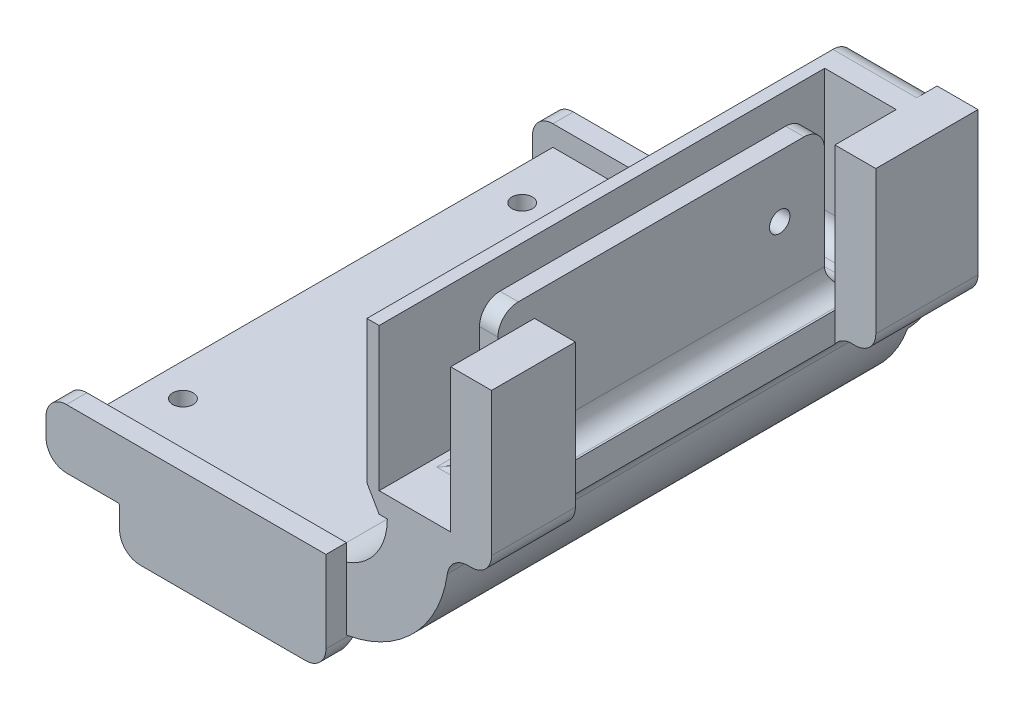
SolidWorks part; units mm, degrees
ref_plane "Alzado" through (0, 0, 0) normal (0, 0, 1) x (1, 0, 0)
ref_plane "Planta" through (0, 0, 0) normal (0, 1, 0) x (1, 0, 0)
ref_plane "Vista lateral" through (0, 0, 0) normal (1, 0, 0) x (0, 0, -1)
sketch "Croquis1" plane through (0, 0, 0) normal (0, 0, 1) x (1, 0, 0)
  line L0 (0, 0) -> (0, -5)
  line L1 (15, -20) -> (337, -20)
  line L2 (352, -5) -> (352, 0)
  line L3 (-15, 0) -> (-15, -5)
  line L4 (15, -35) -> (337, -35)
  line L5 (367, -5) -> (367, 0)
  line L6 (-15, 0) -> (0, 0)
  line L7 (352, 0) -> (367, 0)
  arc A0 (352, -5) -> (337, -20) centre (337, -5) cw
  arc A1 (0, -5) -> (15, -20) centre (15, -5) ccw
  arc A2 (-15, -5) -> (15, -35) centre (15, -5) ccw
  arc A3 (367, -5) -> (337, -35) centre (337, -5) cw
  dimension "D1" = 15
  dimension "D2" = 5
  dimension "D4" = 352
  dimension "D3" = 15
extrude "Saliente-Extruir1" add sketch "Croquis1" along normal blind 103
sketch "Croquis2" plane through (0, 0, 0) normal (0, 1, 0) x (1, 0, 0)
  line L0 (0, -103) -> (0, 0) construction
  line L1 (-10, -25.1459) -> (-5, -25.1459)
  line L2 (-10, -25.1459) -> (-10, -75.1459)
  line L3 (-10, -75.1459) -> (-5, -75.1459)
  line L4 (-5, -25.1459) -> (-5, -75.1459)
  line L5 (357, -11.55) -> (362, -11.55)
  line L6 (357, -11.55) -> (357, -91.45)
  line L7 (357, -91.45) -> (362, -91.45)
  line L8 (362, -11.55) -> (362, -91.45)
  line L9 (352, -103) -> (352, 0) construction
  line L10 (352, 0) -> (352, -103) construction
  point P12 (362, -51.5)
  point P17 (352, -51.5)
  dimension "D1" = 5
  dimension "D2" = 50
  dimension "D3" = 5
  dimension "D4" = 79.9
  dimension "D5" = 5
  dimension "D6" = 5
extrude "Saliente-Extruir2" add sketch "Croquis2" along normal blind 35
fillet "Redondeo1" radius 5 8 edges at (362, 0, 51.5) (359.5, 0, 91.45) (357, 0, 51.5) (359.5, 0, 11.55) (-7.5, 0, 25.1459) (-10, 0, 50.1459) (-7.5, 0, 75.1459) (-5, 0, 50.1459)
fillet "Redondeo2" radius 5 4 edges at (-7.5, 35, 25.1459) (-7.5, 35, 75.1459) (359.5, 35, 11.55) (359.5, 35, 91.45)
ref_plane "Plano1" through (15, 0, 0) normal (1, 0, 0) x (0, 0, -1)
sketch "Croquis3" plane through (15, 0, 0) normal (1, 0, 0) x (0, 0, -1)
  line L0 (-103, -35) -> (0, -35) construction
  line L1 (-76.5, -35) -> (-70.5, -35)
  line L2 (-76.5, -35) -> (-76.5, -43)
  line L3 (-76.5, -43) -> (-26.5, -43)
  line L4 (-26.5, -35) -> (-26.5, -43)
  line L5 (-103, -35) -> (-70.5, -35) construction
  line L6 (-51.5, -33) -> (-51.5, -5) construction
  line L7 (-103, -5) -> (0, -5) construction
  line L8 (-32.5, -35) -> (-26.5, -35)
  line L10 (-70.5, -35) -> (-70.5, -39)
  line L11 (-70.5, -39) -> (-32.5, -39)
  line L12 (-32.5, -35) -> (-32.5, -39)
  line L13 (-51.5, -35) -> (-32.5, -39) construction
  line L14 (-70.5, -39) -> (-51.5, -35) construction
  line L15 (-32.5, -35) -> (0, -35) construction
  dimension "D1" = 50
  dimension "D2" = 8
  dimension "D3" = 38
  dimension "D4" = 4
extrude "Saliente-Extruir3" add sketch "Croquis3" along normal up to vertex (322 mm away) up to point (337, -35, 103)
fillet "Redondeo4" radius 10 2 edges at (176, -35, 76.5) (176, -35, 26.5)
fillet "Redondeo5" radius 10 2 edges at (176, -43, 26.5) (176, -43, 76.5)
sketch "Croquis4" plane through (0, 0, 103) normal (0, 0, 1) x (1, 0, 0)
  line L0 (176, -43) -> (176, 89.8456) construction
  line L1 (337, -43) -> (15, -43) construction
  line L3 (176, 89.8456) -> (296, 89.8456)
  line L4 (176, 89.8456) -> (176, -75.5918)
  line L5 (176, -75.5918) -> (296, -75.5918)
  line L6 (296, 89.8456) -> (296, -75.5918)
  dimension "D1" = 120
extrude "Cortar-Extruir1" cut sketch "Croquis4" against normal through all both and the other way through all
sketch "Croquis8" plane through (296, 0, 0) normal (-1, 0, 0) x (0, 0, 1)
  line L1 (103, -20) -> (0, -20)
  line L2 (103, -20) -> (103, -27)
  line L3 (103, -27) -> (0, -27)
  line L4 (0, -20) -> (0, -27)
  dimension "D1" = 7
extrude "Saliente-Extruir5" add sketch "Croquis8" along normal blind 200
fillet "Redondeo6" radius 15 2 edges at (96, -23.5, 0) (96, -23.5, 103)
sketch "Croquis9" plane through (0, -27, 0) normal (0, -1, 0) x (1, 0, 0)
  line L0 (144.6603, 56.5) -> (147.3397, 56.5)
  line L2 (96, 51.5) -> (106, 51.5) construction
  line L19 (96, 15) -> (96, 88) construction
  line L27 (124.6603, 46.5) -> (127.3397, 46.5)
  line L37 (124.6603, 56.5) -> (127.3397, 56.5)
  line L41 (125.1449, 47.4539) -> (146.3537, 48.864) construction
  line L44 (125.1449, 55.5461) -> (126.807, 55.4356) construction
  line L48 (244.6603, 46.5) -> (247.3397, 46.5)
  line L49 (244.6603, 56.5) -> (247.3397, 56.5)
  line L50 (224.6603, 46.5) -> (227.3397, 46.5)
  line L51 (224.6603, 56.5) -> (227.3397, 56.5)
  line L52 (204.6603, 56.5) -> (207.3397, 56.5)
  line L53 (204.6603, 46.5) -> (207.3397, 46.5)
  line L54 (184.6603, 46.5) -> (187.3397, 46.5)
  line L55 (184.6603, 56.5) -> (187.3397, 56.5)
  line L57 (164.6603, 56.5) -> (167.3397, 56.5)
  line L58 (164.6603, 46.5) -> (167.3397, 46.5)
  line L59 (144.6603, 46.5) -> (147.3397, 46.5)
  arc A21 (124.6603, 56.5) -> (124.6603, 46.5) centre (116, 51.5) ccw
  arc A33 (127.3397, 46.5) -> (144.6603, 46.5) centre (136, 51.5) ccw
  arc A34 (147.3397, 46.5) -> (164.6603, 46.5) centre (156, 51.5) ccw
  arc A35 (167.3397, 46.5) -> (184.6603, 46.5) centre (176, 51.5) ccw
  arc A36 (187.3397, 46.5) -> (204.6603, 46.5) centre (196, 51.5) ccw
  arc A38 (244.6603, 56.5) -> (227.3397, 56.5) centre (236, 51.5) ccw
  arc A39 (247.3397, 46.5) -> (247.3397, 56.5) centre (256, 51.5) ccw
  arc A40 (144.6603, 56.5) -> (127.3397, 56.5) centre (136, 51.5) ccw
  arc A41 (164.6603, 56.5) -> (147.3397, 56.5) centre (156, 51.5) ccw
  arc A42 (184.6603, 56.5) -> (167.3397, 56.5) centre (176, 51.5) ccw
  arc A43 (204.6603, 56.5) -> (187.3397, 56.5) centre (196, 51.5) ccw
  arc A44 (207.3397, 46.5) -> (224.6603, 46.5) centre (216, 51.5) ccw
  arc A45 (227.3397, 46.5) -> (244.6603, 46.5) centre (236, 51.5) ccw
  arc A46 (206.0896, 52.8357) -> (206, 51.5) centre (216, 51.5) ccw [skipped]
  arc A47 (224.6603, 56.5) -> (207.3397, 56.5) centre (216, 51.5) ccw
  point P8 (186, 51.5)
  dimension "D1" = 20
  dimension "D3" = 8
  dimension "D2" = 20
sketch "Croquis10" plane through (362, 0, 0) normal (1, 0, 0) x (0, 0, -1)
  line L0 (-51.5, 35) -> (-51.5, 2.6584) construction
  line L1 (-86.45, 35) -> (-16.55, 35) construction
  line L2 (-80.5, 20) -> (-22.5, 20) construction
  circle A0 centre (-80.5, 20) radius 2.5
  circle A1 centre (-22.5, 20) radius 2.5
  point P4 (-51.5, 20)
  dimension "D1" = 58
  dimension "D3" = 5
  dimension "D4" = 5
  dimension "D2" = 15
extrude "Cortar-Extruir5" cut sketch "Croquis10" against normal through all
extrude "Cortar-Extruir6" cut sketch "Croquis9" against normal blind 10
sketch "Croquis11" plane through (0, -27, 0) normal (0, -1, 0) x (1, 0, 0)
  line L4 (96, 88) -> (96, 15)
  line L5 (111, 0) -> (296, 0)
  line L6 (296, 0) -> (296, 103)
  line L7 (296, 103) -> (111, 103)
  line L8 (96, 88) -> (96, 15)
  line L9 (111, 0) -> (296, 0)
  line L10 (296, 0) -> (296, 103)
  line L11 (296, 103) -> (111, 103)
  arc A2 (96, 15) -> (111, 0) centre (111, 15) ccw
  arc A3 (111, 103) -> (96, 88) centre (111, 88) ccw
  arc A4 (96, 15) -> (111, 0) centre (111, 15) ccw
  arc A5 (111, 103) -> (96, 88) centre (111, 88) ccw
  dimension "D1" = 0
extrude "Cortar-Extruir7" cut sketch "Croquis11" against normal blind 2
sketch "Croquis12" plane through (0, -25, 0) normal (0, -1, 0) x (1, 0, 0)
  line L0 (111, 0) -> (296, 0) construction
  line L1 (296, 103) -> (278.5, 103) construction
  line L2 (296, 103) -> (296, 0) construction
  line L3 (296, 0) -> (278.5, 0) construction
  line L4 (278.5, 103) -> (278.5, 0) construction
  line L5 (287.25, 103) -> (287.25, 0) construction
  line L7 (278.5, 103) -> (48.1838, 103)
  line L8 (278.5, 103) -> (278.5, -29.1349)
  line L9 (278.5, -29.1349) -> (48.1838, -29.1349)
  line L10 (48.1838, 103) -> (48.1838, -29.1349)
  dimension "D1" = 17.5
extrude "Cortar-Extruir8" cut sketch "Croquis12" against normal through all both and the other way through all
sketch "Croquis13" plane through (0, -25, 0) normal (0, -1, 0) x (1, 0, 0)
  line L0 (286.5, 103) -> (286.5, 0) construction
  line L1 (296, 103) -> (278.5, 103) construction
  line L2 (278.5, 0) -> (296, 0) construction
  line L3 (278.5, 0) -> (278.5, 103) construction
  circle A0 centre (286.5, 93) radius 2.5
  circle A1 centre (286.5, 10) radius 2.5
  dimension "D1" = 5
  dimension "D2" = 5
  dimension "D3" = 10
  dimension "D4" = 10
  dimension "D5" = 8
extrude "Cortar-Extruir9" cut sketch "Croquis13" against normal through all both and the other way through all
fillet "Redondeo7" radius 5 1 edges at (296, -25, 51.5)
sketch "Croquis14" plane through (357, 0, 0) normal (-1, 0, 0) x (0, 0, 1)
  line L4 (86.45, 35) -> (16.55, 35)
  line L5 (11.55, 30) -> (11.55, 5)
  line L6 (11.55, 5) -> (91.45, 5)
  line L7 (91.45, 5) -> (91.45, 30)
  line L8 (86.45, 35) -> (16.55, 35)
  line L9 (11.55, 30) -> (11.55, 5)
  line L10 (11.55, 5) -> (91.45, 5)
  line L11 (91.45, 5) -> (91.45, 30)
  arc A2 (16.55, 35) -> (11.55, 30) centre (16.55, 30) ccw
  arc A3 (91.45, 30) -> (86.45, 35) centre (86.45, 30) ccw
  arc A4 (16.55, 35) -> (11.55, 30) centre (16.55, 30) ccw
  arc A5 (91.45, 30) -> (86.45, 35) centre (86.45, 30) ccw
  dimension "D1" = 0
extrude "Cortar-Extruir10" cut sketch "Croquis14" against normal blind 0.5
sketch "Croquis15" plane through (0, 0, 0) normal (0, 0, -1) x (-1, 0, 0)
  line L0 (-296, -43) -> (-296, -39) construction
  line L1 (-296, -39) -> (-296, -35) construction
  line L2 (-296, -35) -> (-296, -30) construction
  line L3 (-278.5, -25) -> (-291, -25) construction
  line L4 (-296, -43) -> (-296, -39)
  line L5 (-296, -39) -> (-296, -35)
  line L6 (-296, -35) -> (-296, -30)
  line L7 (-278.5, -25) -> (-291, -25)
  line L8 (-296.5, -43) -> (-296.5, -39)
  line L9 (-296.5, -39) -> (-296.5, -35)
  line L10 (-296.5, -35) -> (-296.5, -30)
  line L11 (-278.5, -24.5) -> (-291, -24.5)
  line L12 (-278.5, -24.5) -> (-278.5, -25)
  line L13 (-296.5, -43) -> (-296, -43)
  arc A0 (-291, -25) -> (-296, -30) centre (-291, -30) ccw construction
  arc A1 (-291, -25) -> (-296, -30) centre (-291, -30) ccw
  arc A2 (-291, -24.5) -> (-296.5, -30) centre (-291, -30) ccw
  dimension "D1" = 0.5
extrude "Cortar-Extruir11" cut sketch "Croquis15" against normal through all both and the other way through all
sketch "Croquis18" plane through (0, 0, 0) normal (0, 0, -1) x (-1, 0, 0)
  line L8 (-337, -35) -> (-296.5, -35)
  line L9 (-296.5, -35) -> (-296.5, -30)
  line L10 (-291, -24.5) -> (-278.5, -24.5)
  line L11 (-278.5, -24.5) -> (-278.5, -20)
  line L12 (-278.5, -20) -> (-337, -20)
  line L13 (-352, -5) -> (-352, 0)
  line L14 (-352, 0) -> (-367, 0)
  line L15 (-367, 0) -> (-367, -5)
  line L16 (-337, -35) -> (-296.5, -35)
  line L17 (-296.5, -35) -> (-296.5, -30)
  line L18 (-291, -24.5) -> (-278.5, -24.5)
  line L19 (-278.5, -24.5) -> (-278.5, -20)
  line L20 (-278.5, -20) -> (-337, -20)
  line L21 (-352, -5) -> (-352, 0)
  line L22 (-352, 0) -> (-367, 0)
  line L23 (-367, 0) -> (-367, -5)
  arc A3 (-291, -24.5) -> (-296.5, -30) centre (-291, -30) ccw
  arc A4 (-352, -5) -> (-337, -20) centre (-337, -5) ccw
  arc A5 (-367, -5) -> (-337, -35) centre (-337, -5) ccw
  arc A6 (-291, -24.5) -> (-296.5, -30) centre (-291, -30) ccw
  arc A7 (-352, -5) -> (-337, -20) centre (-337, -5) ccw
  arc A8 (-367, -5) -> (-337, -35) centre (-337, -5) ccw
  dimension "D1" = 0
extrude "Saliente-Extruir6" add sketch "Croquis18" along normal blind 0.5
sketch "Croquis19" plane through (0, 0, -0.5) normal (0, 0, -1) x (-1, 0, 0)
  line L0 (-367, 35) -> (-352, 35)
  line L4 (-365.2843, -15) -> (-348.1803, -15)
  line L5 (-367, 0) -> (-367, 35)
  line L6 (-352, 0) -> (-352, 35)
  line L24 (-337, -35) -> (-296.5, -35)
  line L25 (-296.5, -35) -> (-296.5, -30)
  line L26 (-291, -24.5) -> (-278.5, -24.5)
  line L27 (-278.5, -24.5) -> (-278.5, -20)
  line L28 (-278.5, -20) -> (-337, -20)
  line L29 (-352, -5) -> (-352, 0)
  line L30 (-352, 0) -> (-367, 0)
  line L31 (-367, 0) -> (-367, -5)
  line L37 (-352, -5) -> (-352, 0)
  line L39 (-367, 0) -> (-367, -5)
  arc A3 (-367, -5) -> (-337, -35) centre (-337, -5) ccw
  arc A5 (-291, -24.5) -> (-296.5, -30) centre (-291, -30) ccw
  arc A9 (-352, -5) -> (-337, -20) centre (-337, -5) ccw
  arc A10 (-367, -5) -> (-365.2843, -15) centre (-337, -5) ccw
  arc A12 (-352, -5) -> (-348.1803, -15) centre (-337, -5) ccw
  dimension "D1" = 0
extrude "Saliente-Extruir7" add sketch "Croquis19" along normal blind 10
fillet "Redondeo8" radius 5 3 edges at (359.5, 0, -0.5) (359.5, 35, -10.5) (356.7323, -15, -10.5)
sketch "Croquis20" plane through (367, 0, 0) normal (1, 0, 0) x (0, 0, -1)
  line L8 (10.5, -5) -> (10.5, 30)
  line L9 (5.5, 35) -> (0.5, 35)
  line L10 (0.5, 35) -> (0.5, 5)
  line L11 (-4.5, 0) -> (-6.55, 0)
  line L12 (-6.55, 0) -> (-96.45, 0)
  line L13 (-96.45, 0) -> (-103, 0)
  line L14 (-103, 0) -> (-103, -5)
  line L15 (-103, -5) -> (10.5, -5)
  line L16 (10.5, -5) -> (10.5, 30)
  line L17 (5.5, 35) -> (0.5, 35)
  line L18 (0.5, 35) -> (0.5, 5)
  line L19 (-4.5, 0) -> (-6.55, 0)
  line L20 (-6.55, 0) -> (-96.45, 0)
  line L21 (-96.45, 0) -> (-103, 0)
  line L22 (-103, 0) -> (-103, -5)
  line L23 (-103, -5) -> (10.5, -5)
  arc A2 (10.5, 30) -> (5.5, 35) centre (5.5, 30) ccw
  arc A3 (-4.5, 0) -> (0.5, 5) centre (-4.5, 5) ccw
  arc A4 (10.5, 30) -> (5.5, 35) centre (5.5, 30) ccw
  arc A5 (-4.5, 0) -> (0.5, 5) centre (-4.5, 5) ccw
  dimension "D1" = 0
extrude "Saliente-Extruir8" add sketch "Croquis20" along normal blind 0.5
sketch "Croquis21" plane through (367.5, 0, 0) normal (1, 0, 0) x (0, 0, -1)
  line L0 (5.5, 35) -> (0.5, 35) construction
  line L1 (10.5, -5) -> (-14.5, -5)
  line L2 (10.5, -5) -> (10.5, 35)
  line L3 (10.5, 35) -> (-14.5, 35)
  line L4 (-14.5, -5) -> (-14.5, 35)
  line L5 (-86.45, 35) -> (-16.55, 35) construction
  line L6 (-103, -5) -> (-88, -5)
  line L7 (-103, -5) -> (-103, 35)
  line L8 (-103, 35) -> (-88, 35)
  line L9 (-88, -5) -> (-88, 35)
  line L10 (0.5, 35) -> (0.5, 5) construction
  dimension "D1" = 15
  dimension "D2" = 15
extrude "Saliente-Extruir9" add sketch "Croquis21" along normal blind 10
fillet "Redondeo9" radius 5 3 edges at (367, -5, 46.25) (377.5, -5, 2) (377.5, -5, 95.5)
sketch "Croquis22" plane through (352, 0, 0) normal (-1, 0, 0) x (0, 0, 1)
  line L8 (-0.5, 35) -> (-5.5, 35)
  line L9 (-10.5, 30) -> (-10.5, -5)
  line L10 (-10.5, -5) -> (103, -5)
  line L11 (103, -5) -> (103, 0)
  line L12 (103, 0) -> (96.45, 0)
  line L13 (96.45, 0) -> (6.55, 0)
  line L14 (6.55, 0) -> (4.5, 0)
  line L15 (-0.5, 5) -> (-0.5, 35)
  line L16 (-0.5, 35) -> (-5.5, 35)
  line L17 (-10.5, 30) -> (-10.5, -5)
  line L18 (-10.5, -5) -> (103, -5)
  line L19 (103, -5) -> (103, 0)
  line L20 (103, 0) -> (96.45, 0)
  line L21 (96.45, 0) -> (6.55, 0)
  line L22 (6.55, 0) -> (4.5, 0)
  line L23 (-0.5, 5) -> (-0.5, 35)
  arc A2 (-5.5, 35) -> (-10.5, 30) centre (-5.5, 30) ccw
  arc A3 (-0.5, 5) -> (4.5, 0) centre (4.5, 5) ccw
  arc A4 (-5.5, 35) -> (-10.5, 30) centre (-5.5, 30) ccw
  arc A5 (-0.5, 5) -> (4.5, 0) centre (4.5, 5) ccw
  dimension "D1" = 0
extrude "Saliente-Extruir10" add sketch "Croquis22" along normal blind 2
sketch "Croquis23" plane through (350, 0, 0) normal (-1, 0, 0) x (0, 0, 1)
  line L0 (-0.5, 35) -> (103, 35)
  line L1 (103, 0) -> (103, 35)
  line L6 (-0.5, 5) -> (-0.5, 35)
  line L7 (-0.5, 35) -> (-5.5, 35)
  line L8 (-10.5, 30) -> (-10.5, -5)
  line L9 (-10.5, -5) -> (103, -5)
  line L10 (103, -5) -> (103, 0)
  line L11 (103, 0) -> (4.5, 0)
  line L13 (-0.5, 35) -> (-5.5, 35)
  line L14 (-10.5, 30) -> (-10.5, -5)
  line L15 (-10.5, -5) -> (103, -5)
  line L16 (103, -5) -> (103, 0)
  arc A2 (-5.5, 35) -> (-10.5, 30) centre (-5.5, 30) ccw
  arc A3 (-0.5, 5) -> (4.5, 0) centre (4.5, 5) ccw
  arc A4 (-5.5, 35) -> (-10.5, 30) centre (-5.5, 30) ccw
  dimension "D1" = 0
extrude "Saliente-Extruir11" add sketch "Croquis23" along normal blind 3
chamfer "Chaflán1" distance 3 angle 60 1 edges at (347, -5, 46.25) first distance on face at (349.5, -5, 46.25)
sketch "Croquis24" plane through (0, 0, 103) normal (0, 0, 1) x (1, 0, 0)
  line L15 (347, 35) -> (347, 0.1962)
  line L16 (347, 0.1962) -> (350, -5)
  line L17 (350, -5) -> (352, -5)
  line L18 (337, -20) -> (278.5, -20)
  line L19 (278.5, -20) -> (278.5, -24.5)
  line L20 (278.5, -24.5) -> (291, -24.5)
  line L21 (296.5, -30) -> (296.5, -35)
  line L22 (296.5, -35) -> (337, -35)
  line L23 (371.641, -5) -> (372.5, -5)
  line L24 (377.5, 0) -> (377.5, 35)
  line L25 (377.5, 35) -> (367.5, 35)
  line L26 (367.5, 35) -> (367.5, 0)
  line L27 (367.5, 0) -> (350, 0)
  line L28 (350, 0) -> (350, 35)
  line L29 (350, 35) -> (347, 35)
  line L30 (347, 35) -> (347, 0.1962)
  line L31 (347, 0.1962) -> (350, -5)
  line L32 (350, -5) -> (352, -5)
  line L33 (337, -20) -> (278.5, -20)
  line L34 (278.5, -20) -> (278.5, -24.5)
  line L35 (278.5, -24.5) -> (291, -24.5)
  line L36 (296.5, -30) -> (296.5, -35)
  line L37 (296.5, -35) -> (337, -35)
  line L38 (371.641, -5) -> (372.5, -5)
  line L39 (377.5, 0) -> (377.5, 35)
  line L40 (377.5, 35) -> (367.5, 35)
  line L41 (367.5, 35) -> (367.5, 0)
  line L42 (367.5, 0) -> (350, 0)
  line L43 (350, 0) -> (350, 35)
  line L44 (350, 35) -> (347, 35)
  arc A5 (337, -20) -> (352, -5) centre (337, -5) ccw
  arc A6 (296.5, -30) -> (291, -24.5) centre (291, -30) ccw
  arc A7 (337, -35) -> (366.6923, -9.2857) centre (337, -5) ccw
  arc A8 (371.641, -5) -> (366.6923, -9.2857) centre (371.641, -10) ccw
  arc A9 (372.5, -5) -> (377.5, 0) centre (372.5, 0) ccw
  arc A10 (337, -20) -> (352, -5) centre (337, -5) ccw
  arc A11 (296.5, -30) -> (291, -24.5) centre (291, -30) ccw
  arc A12 (337, -35) -> (366.6923, -9.2857) centre (337, -5) ccw
  arc A13 (371.641, -5) -> (366.6923, -9.2857) centre (371.641, -10) ccw
  arc A14 (372.5, -5) -> (377.5, 0) centre (372.5, 0) ccw
  dimension "D1" = 0
extrude "Saliente-Extruir12" add sketch "Croquis24" along normal blind 0.5
sketch "Croquis25" plane through (0, 0, -0.5) normal (0, 0, -1) x (-1, 0, 0)
  line L6 (-348.1803, -15) -> (-365.2843, -15)
  line L7 (-337, -35) -> (-296.5, -35)
  line L8 (-296.5, -35) -> (-296.5, -30)
  line L9 (-291, -24.5) -> (-278.5, -24.5)
  line L10 (-278.5, -24.5) -> (-278.5, -20)
  line L11 (-278.5, -20) -> (-337, -20)
  line L12 (-348.1803, -15) -> (-365.2843, -15)
  line L13 (-337, -35) -> (-296.5, -35)
  line L14 (-296.5, -35) -> (-296.5, -30)
  line L15 (-291, -24.5) -> (-278.5, -24.5)
  line L16 (-278.5, -24.5) -> (-278.5, -20)
  line L17 (-278.5, -20) -> (-337, -20)
  arc A3 (-365.2843, -15) -> (-337, -35) centre (-337, -5) ccw
  arc A4 (-291, -24.5) -> (-296.5, -30) centre (-291, -30) ccw
  arc A5 (-348.1803, -15) -> (-337, -20) centre (-337, -5) ccw
  arc A6 (-365.2843, -15) -> (-337, -35) centre (-337, -5) ccw
  arc A7 (-291, -24.5) -> (-296.5, -30) centre (-291, -30) ccw
  arc A8 (-348.1803, -15) -> (-337, -20) centre (-337, -5) ccw
  dimension "D1" = 0
extrude "Saliente-Extruir13" add sketch "Croquis25" along normal blind 5
sketch "Croquis26" plane through (0, 0, 103.5) normal (0, 0, 1) x (1, 0, 0)
  line L15 (350, 35) -> (347, 35)
  line L16 (347, 35) -> (347, 0.1962)
  line L17 (347, 0.1962) -> (350, -5)
  line L18 (350, -5) -> (352, -5)
  line L19 (337, -20) -> (278.5, -20)
  line L20 (278.5, -20) -> (278.5, -24.5)
  line L21 (278.5, -24.5) -> (291, -24.5)
  line L22 (296.5, -30) -> (296.5, -35)
  line L23 (296.5, -35) -> (337, -35)
  line L24 (371.641, -5) -> (372.5, -5)
  line L25 (377.5, 0) -> (377.5, 35)
  line L26 (377.5, 35) -> (367.5, 35)
  line L27 (367.5, 35) -> (367.5, 0)
  line L28 (367.5, 0) -> (350, 0)
  line L29 (350, 0) -> (350, 35)
  line L30 (350, 35) -> (347, 35)
  line L31 (347, 35) -> (347, 0.1962)
  line L32 (347, 0.1962) -> (350, -5)
  line L33 (350, -5) -> (352, -5)
  line L34 (337, -20) -> (278.5, -20)
  line L35 (278.5, -20) -> (278.5, -24.5)
  line L36 (278.5, -24.5) -> (291, -24.5)
  line L37 (296.5, -30) -> (296.5, -35)
  line L38 (296.5, -35) -> (337, -35)
  line L39 (371.641, -5) -> (372.5, -5)
  line L40 (377.5, 0) -> (377.5, 35)
  line L41 (377.5, 35) -> (367.5, 35)
  line L42 (367.5, 35) -> (367.5, 0)
  line L43 (367.5, 0) -> (350, 0)
  line L44 (350, 0) -> (350, 35)
  arc A5 (337, -20) -> (352, -5) centre (337, -5) ccw
  arc A6 (296.5, -30) -> (291, -24.5) centre (291, -30) ccw
  arc A7 (337, -35) -> (366.6923, -9.2857) centre (337, -5) ccw
  arc A8 (371.641, -5) -> (366.6923, -9.2857) centre (371.641, -10) ccw
  arc A9 (372.5, -5) -> (377.5, 0) centre (372.5, 0) ccw
  arc A10 (337, -20) -> (352, -5) centre (337, -5) ccw
  arc A11 (296.5, -30) -> (291, -24.5) centre (291, -30) ccw
  arc A12 (337, -35) -> (366.6923, -9.2857) centre (337, -5) ccw
  arc A13 (371.641, -5) -> (366.6923, -9.2857) centre (371.641, -10) ccw
  arc A14 (372.5, -5) -> (377.5, 0) centre (372.5, 0) ccw
  dimension "D1" = 0
extrude "Saliente-Extruir14" add sketch "Croquis26" along normal blind 5
sketch "Croquis27" plane through (0, 0, -5.5) normal (0, 0, -1) x (-1, 0, 0)
  line L0 (-337, -35) -> (-337, -20) construction
  line L1 (-342, -40) -> (-342, -15)
  line L2 (-273.5, -15) -> (-342, -15)
  line L3 (-273.5, -29.5) -> (-273.5, -15)
  line L4 (-291, -29.5) -> (-273.5, -29.5)
  line L5 (-291.5, -40) -> (-291.5, -30)
  line L6 (-348.1803, -15) -> (-365.2843, -15)
  line L7 (-337, -35) -> (-296.5, -35)
  line L8 (-296.5, -35) -> (-296.5, -30)
  line L9 (-291, -24.5) -> (-278.5, -24.5)
  line L10 (-278.5, -24.5) -> (-278.5, -20)
  line L11 (-278.5, -20) -> (-337, -20)
  line L13 (-337, -35) -> (-296.5, -35) construction
  line L14 (-296.5, -35) -> (-296.5, -30) construction
  line L15 (-291, -24.5) -> (-278.5, -24.5) construction
  line L16 (-278.5, -24.5) -> (-278.5, -20) construction
  line L17 (-278.5, -20) -> (-337, -20) construction
  line L18 (-342, -40) -> (-291.5, -40)
  arc A0 (-291, -29.5) -> (-291.5, -30) centre (-291, -30) ccw
  arc A3 (-348.1803, -15) -> (-337, -20) centre (-337, -5) ccw
  arc A4 (-365.2843, -15) -> (-337, -35) centre (-337, -5) ccw
  arc A5 (-291, -24.5) -> (-296.5, -30) centre (-291, -30) ccw
  arc A8 (-291, -24.5) -> (-296.5, -30) centre (-291, -30) ccw construction
  dimension "D1" = 0
  dimension "D2" = 5
extrude "Saliente-Extruir15" add sketch "Croquis27" along normal blind 5
sketch "Croquis28" plane through (0, 0, 108.5) normal (0, 0, 1) x (1, 0, 0)
  line L6 (291.5, -40) -> (342, -40)
  line L7 (291.5, -30) -> (291.5, -40)
  line L8 (273.5, -29.5) -> (291, -29.5)
  line L9 (273.5, -15) -> (273.5, -29.5)
  line L10 (342, -15) -> (273.5, -15)
  line L11 (342, -40) -> (342, -15)
  line L12 (291.5, -40) -> (342, -40)
  line L13 (291.5, -30) -> (291.5, -40)
  line L14 (273.5, -29.5) -> (291, -29.5)
  line L15 (273.5, -15) -> (273.5, -29.5)
  line L16 (342, -15) -> (273.5, -15)
  line L17 (342, -40) -> (342, -15)
  arc A1 (291.5, -30) -> (291, -29.5) centre (291, -30) ccw
  arc A2 (291.5, -30) -> (291, -29.5) centre (291, -30) ccw
  dimension "D1" = 0
extrude "Saliente-Extruir16" add sketch "Croquis28" along normal blind 5
fillet "Redondeo10" radius 5 8 edges at (273.5, -15, 111) (273.5, -29.5, 111) (291.5, -40, 111) (342, -40, 111) (342, -40, -8) (291.5, -40, -8) (273.5, -29.5, -8) (273.5, -15, -8)
sketch "Croquis29" plane through (0, -43, 0) normal (0, -1, 0) x (1, 0, 0)
  line L0 (296.5, 108.5) -> (296.5, 86.298) construction
  line L1 (296.5, 102.1512) -> (337, 102.1512)
  line L2 (296.5, 102.1512) -> (296.5, 7.5163)
  line L3 (296.5, 7.5163) -> (337, 7.5163)
  line L4 (337, 102.1512) -> (337, 7.5163)
  line L5 (337, 16.702) -> (337, -5.5) construction
extrude "Cortar-Extruir12" cut sketch "Croquis29" against normal up to surface (8 mm away) up to face at (316.75, -35, 51.5)
fillet "Redondeo11" radius 5 4 edges at (339.5088, -34.8949, -5.5) (339.5088, -34.8949, 108.5) (316.75, -35, -5.5) (316.75, -35, 108.5)
